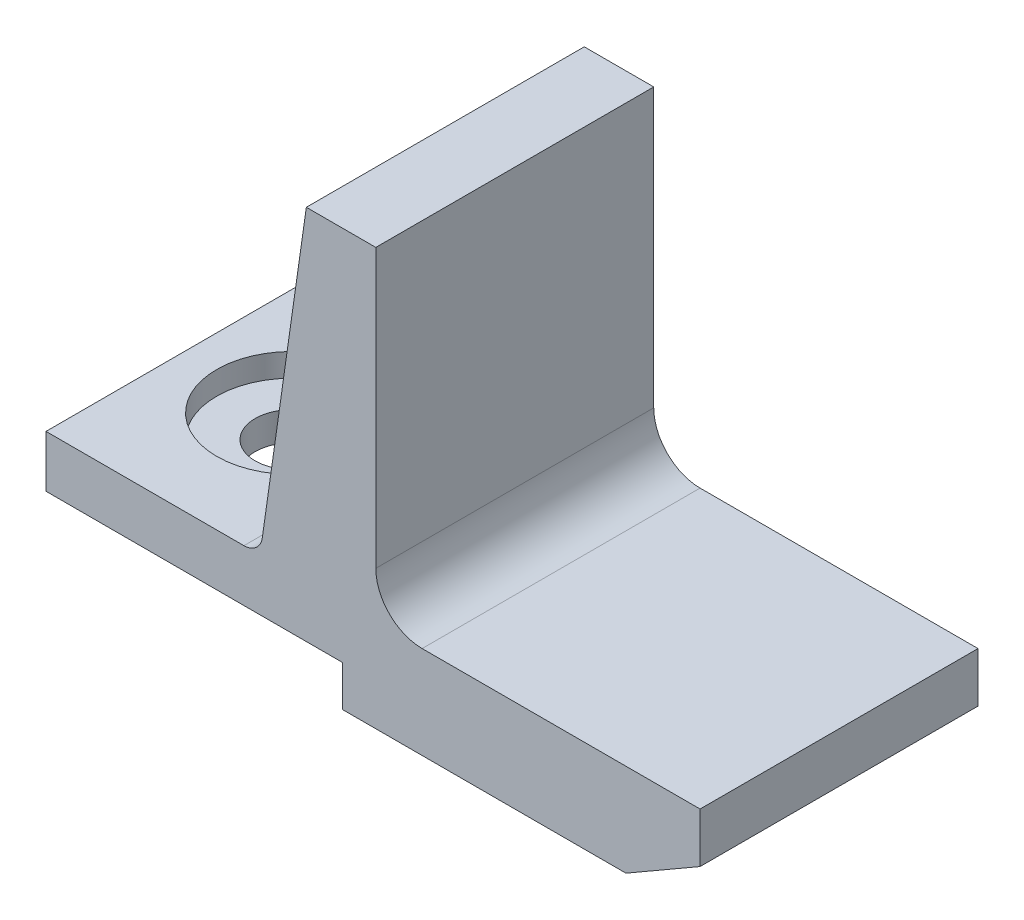
SolidWorks part; units mm, degrees
ref_plane "Front Plane" through (0, 0, 0) normal (0, 0, 1) x (1, 0, 0)
ref_plane "Top Plane" through (0, 0, 0) normal (0, 1, 0) x (1, 0, 0)
ref_plane "Right Plane" through (0, 0, 0) normal (1, 0, 0) x (0, 0, -1)
sketch "Sketch1" plane through (0, 0, 0) normal (0, 0, 1) x (1, 0, 0)
  line L0 (0, 0) -> (44.45, 0)
  line L1 (44.45, 0) -> (44.45, -12.7)
  line L2 (44.45, -12.7) -> (-4.572, -12.7)
  line L3 (-45.212, -7.112) -> (-45.212, 0)
  line L4 (-45.212, 0) -> (-15.875, 0)
  line L5 (-15.875, 0) -> (-9.525, 44.45)
  line L6 (-9.525, 44.45) -> (0, 44.45)
  line L7 (0, 44.45) -> (0, 0)
  line L8 (-4.572, -12.7) -> (-4.572, -7.112)
  line L9 (-4.572, -7.112) -> (-45.212, -7.112)
  dimension "D1" = 44.45
  dimension "D2" = 44.45
  dimension "D3" = 12.7
  dimension "D4" = 29.337
  dimension "D5" = 9.525
  dimension "D6" = 5.588
  dimension "D7" = 40.64
  dimension "D8" = 15.875
extrude "Boss-Extrude1" add sketch "Sketch1" along normal blind 38.1
hole_wizard "CBORE for 3/8 Binding Head Machine Screw1" positions "Sketch6" profile "Sketch3" counterbore size "3/8" standard "ANSI Inch" end condition through all
sketch "Sketch6" plane through (0, 0, 0) normal (0, 1, 0) x (1, 0, 0)
  line L0 (-15.875, 0) -> (-45.212, 0) construction
  line L1 (-45.212, -38.1) -> (-45.212, 0) construction
  point P0 (-30.5435, -19.05)
  point P5 (-30.5435, 0)
  point P8 (-45.212, -19.05)
sketch "Sketch3" plane through (-30.5435, 0, 19.05) normal (1, 0, 0) x (0, 0, 1)
  line L0 (0, 0) -> (0, 12.7)
  line L1 (0, 12.7) -> (5.0419, 12.7)
  line L3 (5.0419, 12.7) -> (5.0419, 3.175)
  line L4 (10.3187, 3.175) -> (5.0419, 3.175)
  line L5 (10.3187, 3.175) -> (10.3187, 0)
  line L7 (10.3187, 0) -> (0, 0)
  line L11 (0, 0) -> (0, 107.95) construction
  dimension "Thru Hole Dia." = 10.0838
  dimension "Thru Hole Depth" = 12.7
  dimension "C'Bore Depth" = 3.175
chamfer "Chamfer1" distance 10.16 angle 30 1 edges at (44.45, -12.7, 19.05) first distance on face at (19.939, -12.7, 19.05)
fillet "Fillet1" radius 2.54 1 edges at (-15.875, 0, 19.05)
fillet "Fillet2" radius 6.35 1 edges at (0, 0, 19.05)
